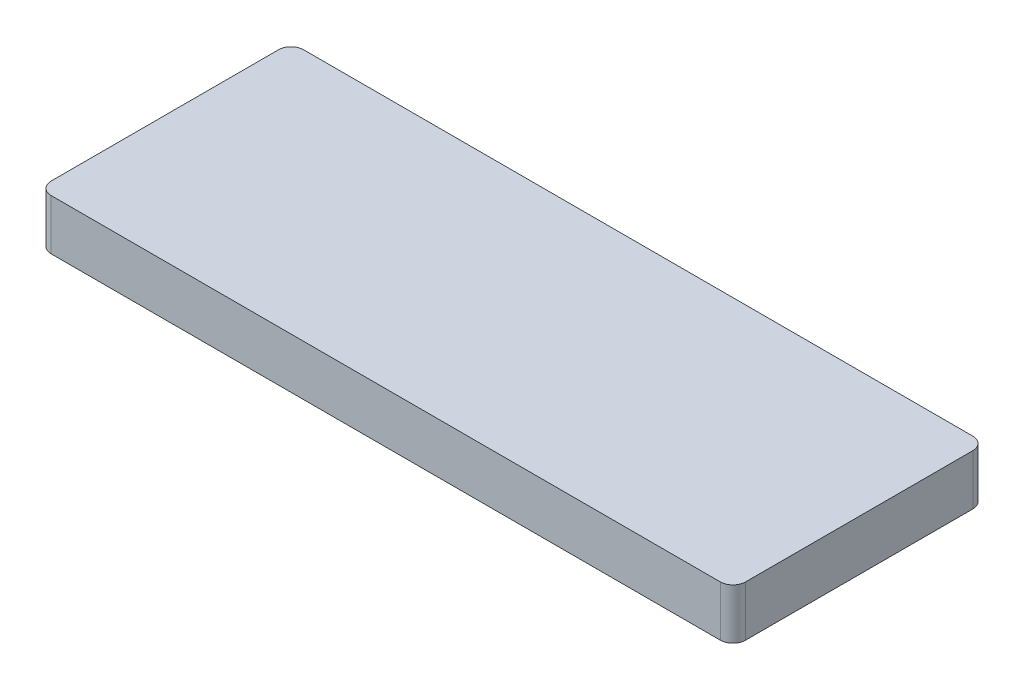
SolidWorks part; units mm, degrees
ref_plane "Front Plane" through (0, 0, 0) normal (0, 0, 1) x (1, 0, 0)
ref_plane "Top Plane" through (0, 0, 0) normal (0, 1, 0) x (1, 0, 0)
ref_plane "Right Plane" through (0, 0, 0) normal (1, 0, 0) x (0, 0, -1)
sketch "Sketch1" plane through (0, 0, 0) normal (0, 1, 0) x (1, 0, 0)
  line L0 (0, 0) -> (34.925, 0)
  line L1 (34.925, 0) -> (34.925, 12.7)
  line L2 (34.925, 12.7) -> (0, 12.7)
  line L3 (0, 12.7) -> (0, 0)
  dimension "D1" = 34.925
  dimension "D2" = 12.7
extrude "Boss-Extrude1" add sketch "Sketch1" along normal blind 2.54
fillet "Fillet1" radius 0.635 4 edges at (0, 1.27, -12.7) (34.925, 1.27, -12.7) (34.925, 1.27, 0) (0, 1.27, 0)
shell "Shell1" thickness 0.635 removed face at (17.4625, 0, -6.35)
sketch "Sketch2" plane through (0, 1.905, 0) normal (0, -1, 0) x (-1, 0, 0)
  line L0 (-0.635, 6.35) -> (-34.29, 6.35) construction
  line L1 (-0.635, 12.065) -> (-0.635, 0.635) construction
  line L2 (-34.29, 0.635) -> (-34.29, 12.065) construction
  line L3 (-17.4625, 0.635) -> (-17.4625, 12.065) construction
  line L4 (-0.635, 0.635) -> (-34.29, 0.635) construction
  line L5 (-34.29, 12.065) -> (-0.635, 12.065) construction
  circle A0 centre (-17.4625, 6.35) radius 2.54
  dimension "D1" = 5.08
extrude "Boss-Extrude2" add sketch "Sketch2" along normal up to surface (1.905 mm away) up to face at (17.4625, 0, -6.35)
